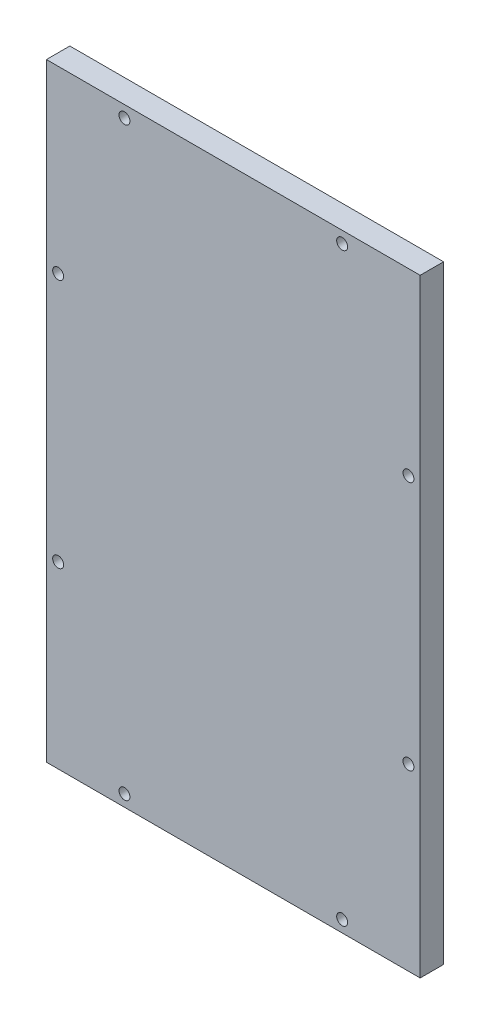
SolidWorks part; units mm, degrees
ref_plane "前视基准面" through (0, 0, 0) normal (0, 0, 1) x (1, 0, 0)
ref_plane "上视基准面" through (0, 0, 0) normal (0, 1, 0) x (1, 0, 0)
ref_plane "右视基准面" through (0, 0, 0) normal (1, 0, 0) x (0, 0, -1)
other "Configuration Table"
sketch "草图1" plane through (0, 0, 0) normal (0, 0, 1) x (1, 0, 0)
  line L61 (-23.95, 39) -> (23.95, 39)
  line L62 (-23.95, 39) -> (-23.95, -39)
  line L63 (-23.95, -39) -> (23.95, -39)
  line L64 (23.95, 39) -> (23.95, -39)
  point P4 (0, 39)
  point P5 (-23.95, 0)
  dimension "D1" = 78
  dimension "D2" = 47.9
extrude "凸台-拉伸1" add sketch "草图1" along normal blind 3
sketch "草图2" plane through (0, 0, 0) normal (0, 0, -1) x (-1, 0, 0)
  line L0 (-13.95, 37.5) -> (-23.95, 37.5)
  line L1 (-23.95, -39) -> (-23.95, 39) construction
  line L2 (23.95, -39) -> (-23.95, -39) construction
  line L3 (23.95, 39) -> (23.95, -39) construction
  line L4 (-13.95, 37.5) -> (-13.95, 39)
  line L5 (-23.95, 39) -> (23.95, 39) construction
  line L6 (13.95, -37.5) -> (23.95, -37.5)
  line L7 (13.95, -37.5) -> (13.95, -39)
  line L9 (-22.45, 16) -> (-22.45, 39)
  line L10 (-22.45, 16) -> (-23.95, 16)
  line L11 (22.45, -16) -> (22.45, -39)
  line L12 (22.45, -16) -> (23.95, -16)
  circle A0 centre (-13.95, 37.5) radius 1
  circle A1 centre (-13.95, 37.5) radius 0.7
  circle A2 centre (13.95, 37.5) radius 1
  circle A3 centre (13.95, 37.5) radius 0.7
  circle A4 centre (-13.95, -37.5) radius 1
  circle A5 centre (-13.95, -37.5) radius 0.7
  circle A6 centre (13.95, -37.5) radius 1
  circle A7 centre (13.95, -37.5) radius 0.7
  circle A8 centre (-22.45, 16) radius 0.7
  circle A9 centre (-22.45, -16) radius 0.7
  circle A10 centre (22.45, 16) radius 0.7
  circle A11 centre (22.45, -16) radius 0.7
  circle A12 centre (-22.45, 16) radius 1
  circle A13 centre (22.45, 16) radius 1
  circle A14 centre (-22.45, -16) radius 1
  circle A15 centre (22.45, -16) radius 1
  point P11 (0, 0)
  point P35 (0, 0)
  point P43 (0, 0)
  point P45 (0, 0)
  point P46 (-17.5152, 12.3989)
  point P47 (12.3222, -17.6187)
  point P48 (13.359, -17.8072)
  point P49 (0, 0)
  point P50 (-19.9997, 15.2182)
  dimension "D3" = 1.4
  dimension "D4" = 2
  dimension "D1" = 1.5
  dimension "D2" = 10
  dimension "D5" = 23
extrude "切除-拉伸1" cut sketch "草图2" against normal through all contours A9 | A8 | A1 | A3 | A5 | A7 | A10 | A11
extrude "切除-拉伸2" cut sketch "草图2<3>" against normal blind 1.5 contours A12 | A0 | A2 | A13 | A15 | A6 | A4 | A14
sketch "草图2<3>" plane through (0, 0, 0) normal (0, 0, -1) x (-1, 0, 0) same geometry as "草图2"
